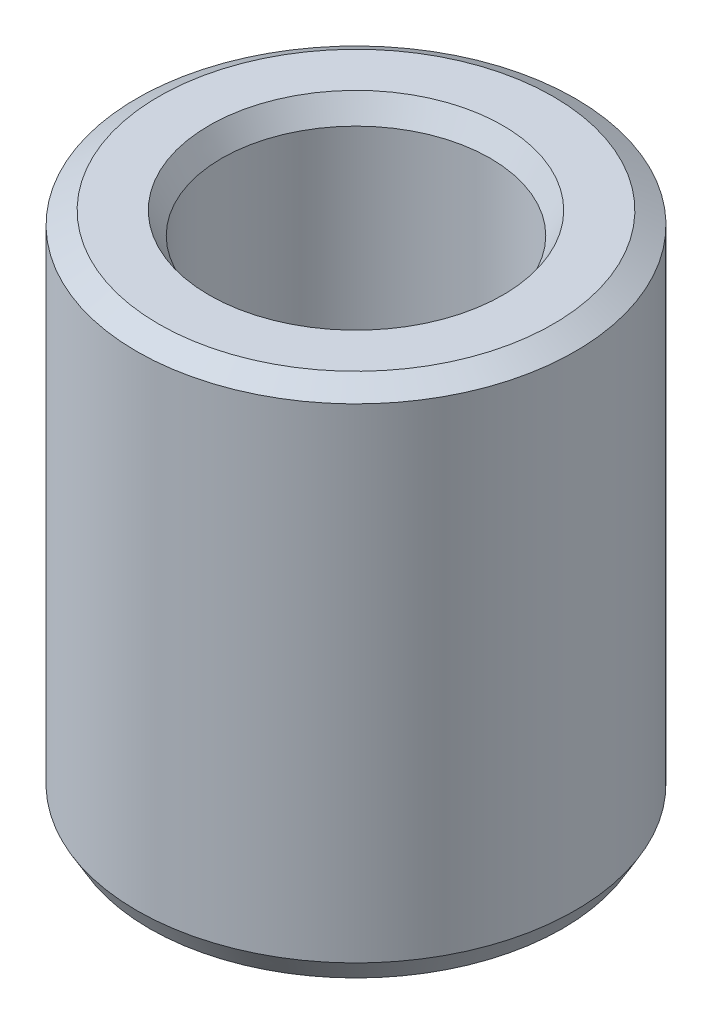
SolidWorks part; units mm, degrees
ref_plane "Front Plane" through (0, 0, 0) normal (0, 0, 1) x (1, 0, 0)
ref_plane "Top Plane" through (0, 0, 0) normal (0, 1, 0) x (1, 0, 0)
ref_plane "Right Plane" through (0, 0, 0) normal (1, 0, 0) x (0, 0, -1)
sketch "Sketch1" plane through (0, 0, 0) normal (0, 1, 0) x (1, 0, 0)
  circle A0 centre (0, 0) radius 47.5
  dimension "SLEEVE_OD" = 95
extrude "Boss-Extrude1" add sketch "Sketch1" along normal blind 112.4332
sketch "Sketch2" plane through (0, 0, 0) normal (0, 1, 0) x (1, 0, 0)
  circle A0 centre (0, 0) radius 29.0803
  dimension "BORE_D" = 58.1607
extrude "Cut-Extrude1" cut sketch "Sketch2" along normal through all
chamfer "Chamfer1" distance 2.7512 angle 60 4 edges at (0, 112.4332, 29.0803) (0, 0, 29.0803) (0, 0, 47.5) (0, 112.4332, 47.5) first distance on face at (0, 112.4332, 29.0803) first distance on face at (0, 0, 29.0803) first distance on face at (0, 112.4332, 47.5)
